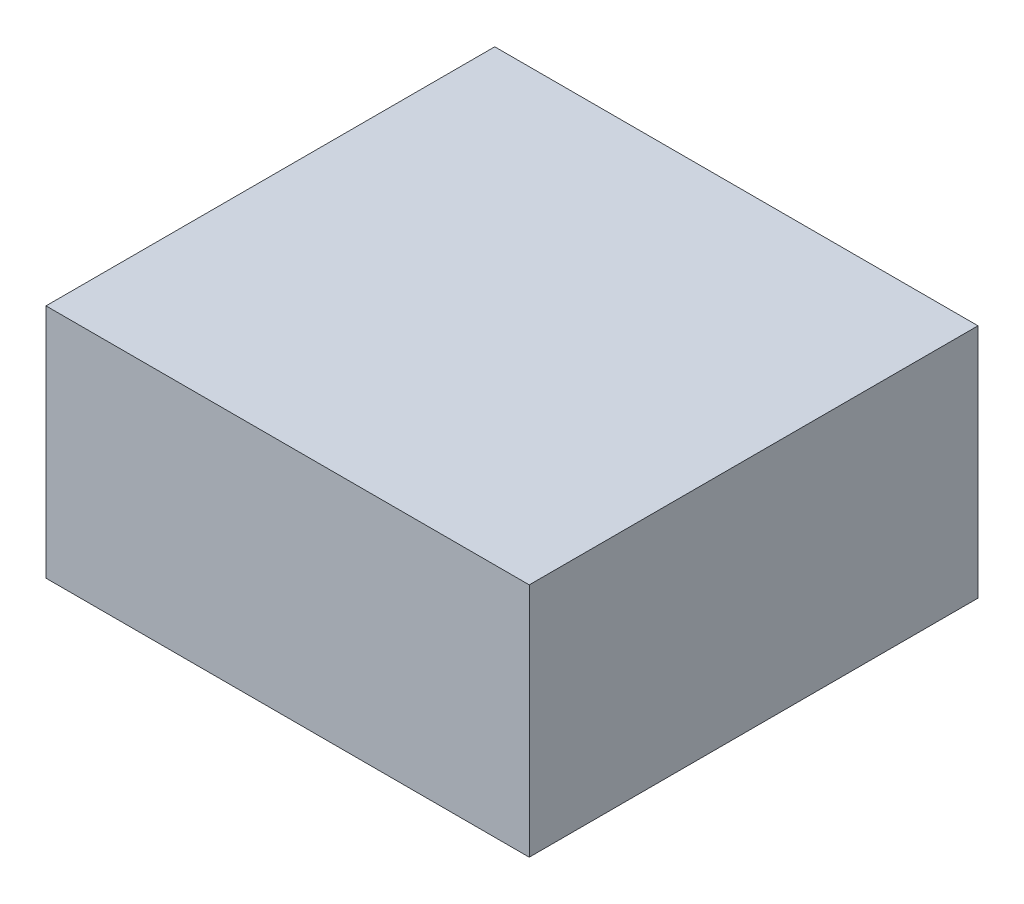
SolidWorks part; units mm, degrees
ref_plane "Front Plane" through (0, 0, 0) normal (0, 0, 1) x (1, 0, 0)
ref_plane "Top Plane" through (0, 0, 0) normal (0, 1, 0) x (1, 0, 0)
ref_plane "Right Plane" through (0, 0, 0) normal (1, 0, 0) x (0, 0, -1)
sketch "Sketch1" plane through (0, 0, 0) normal (0, 1, 0) x (1, 0, 0)
  line L1 (76.835, -71.3486) -> (-76.835, -71.3486)
  line L2 (76.835, -71.3486) -> (76.835, 71.3486)
  line L3 (76.835, 71.3486) -> (-76.835, 71.3486)
  line L4 (-76.835, -71.3486) -> (-76.835, 71.3486)
  line L5 (76.835, -71.3486) -> (-76.835, 71.3486) construction
  line L6 (76.835, 71.3486) -> (-76.835, -71.3486) construction
  point P0 (0, 0)
  dimension "D1" = 142.6972
  dimension "D2" = 153.67
extrude "Boss-Extrude1" add sketch "Sketch1" along normal blind 75.0062
